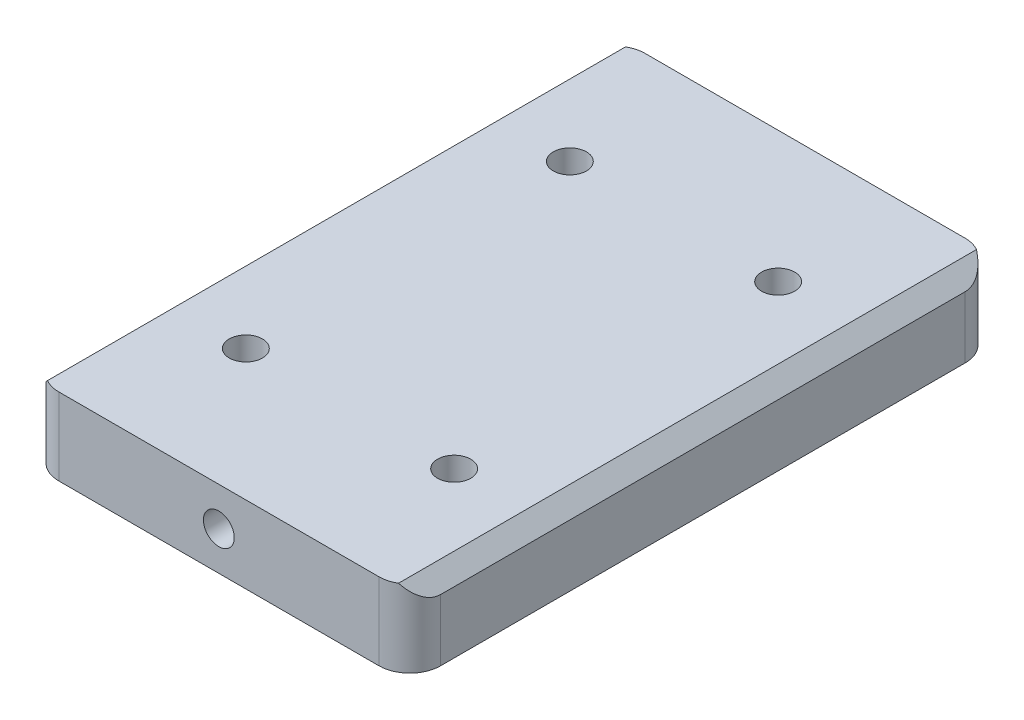
SolidWorks part; units mm, degrees
note: The reader was unsure of these and kept them because the rebuilt part matched: shared geometry of "Sketch1<3>", "Sketch1<5>".
ref_plane "Front Plane" through (0, 0, 0) normal (0, 0, 1) x (1, 0, 0)
ref_plane "Top Plane" through (0, 0, 0) normal (0, 1, 0) x (1, 0, 0)
ref_plane "Right Plane" through (0, 0, 0) normal (1, 0, 0) x (0, 0, -1)
sketch "Base" plane through (0, 0, 0) normal (0, 1, 0) x (1, 0, 0)
  line L0 (0, 0) -> (12.375, 0) construction
  line L1 (-12.375, 19) -> (12.375, 19)
  line L2 (-12.375, 19) -> (-12.375, -19)
  line L3 (-12.375, -19) -> (12.375, -19)
  line L4 (12.375, 19) -> (12.375, -19)
  line L5 (-12.375, 19) -> (12.375, -19) construction
  line L6 (-12.375, -19) -> (12.375, 19) construction
  line L7 (-6.75, 10.5) -> (-6.75, -10.5) construction
  line L8 (-6.75, 10.5) -> (6.75, 10.5) construction
  line L9 (-6.75, -10.5) -> (6.75, -10.5) construction
  line L10 (6.75, 10.5) -> (6.75, -10.5) construction
  line L11 (0, 11.2146) -> (0, -9.7854) construction
  line L12 (-4.75, 9.3453) -> (-4.75, 11.6547)
  line L13 (-4.75, 11.6547) -> (-6.75, 12.8094)
  line L14 (-6.75, 12.8094) -> (-8.75, 11.6547)
  line L15 (-8.75, 11.6547) -> (-8.75, 9.3453)
  line L16 (-8.75, 9.3453) -> (-6.75, 8.1906)
  line L17 (-6.75, 8.1906) -> (-4.75, 9.3453)
  line L18 (8.75, 11.6547) -> (6.75, 12.8094)
  line L19 (6.75, 12.8094) -> (4.75, 11.6547)
  line L20 (4.75, 11.6547) -> (4.75, 9.3453)
  line L21 (4.75, 9.3453) -> (6.75, 8.1906)
  line L22 (6.75, 8.1906) -> (8.75, 9.3453)
  line L23 (8.75, 9.3453) -> (8.75, 11.6547)
  line L24 (8.75, -11.6547) -> (8.75, -9.3453)
  line L25 (8.75, -9.3453) -> (6.75, -8.1906)
  line L26 (6.75, -8.1906) -> (4.75, -9.3453)
  line L27 (4.75, -9.3453) -> (4.75, -11.6547)
  line L28 (4.75, -11.6547) -> (6.75, -12.8094)
  line L29 (6.75, -12.8094) -> (8.75, -11.6547)
  line L30 (-4.75, -11.6547) -> (-4.75, -9.3453)
  line L31 (-4.75, -9.3453) -> (-6.75, -8.1906)
  line L32 (-6.75, -8.1906) -> (-8.75, -9.3453)
  line L33 (-8.75, -9.3453) -> (-8.75, -11.6547)
  line L34 (-8.75, -11.6547) -> (-6.75, -12.8094)
  line L35 (-6.75, -12.8094) -> (-4.75, -11.6547)
  line L36 (-6.75, 0) -> (6.75, 0) construction
  circle A0 centre (-6.75, 10.5) radius 1.075
  circle A1 centre (6.75, 10.5) radius 1.075
  circle A2 centre (6.75, -10.5) radius 1.075
  circle A3 centre (-6.75, -10.5) radius 1.075
  circle A4 centre (-6.75, 10.5) radius 2 construction
  circle A5 centre (6.75, 10.5) radius 2 construction
  circle A6 centre (6.75, -10.5) radius 2 construction
  circle A7 centre (-6.75, -10.5) radius 2 construction
  point P0 (0, 0)
  point P45 (0, 0)
  dimension "D5" = 2.15
  dimension "D6" = 4
  dimension "D1" = 24.75
  dimension "D2" = 38
  dimension "D3" = 13.5
  dimension "D4" = 21
extrude "Boss-Extrude1" add sketch "Base" along normal blind 5 contours L4 L1 L2 L3 L35 L34 L33 L32 L31 L30 L29 L28 L27 L26 L25 L24 L23 L22 L21 L20 L19 L18 L17 L16 L15 L14 L13 L12 | A3 | L28 L29 L24 L25 L26 L27 A2 | A2 | L22 L23 L18 L19 L20 L21 A1 | A0 | L16 L17 L12 L13 L14 L15 A0 | A1 | L34 L35 L30 L31 L32 L33 A3
extrude "Cut-Extrude1" cut sketch "Sketch1<3>" along normal blind 2 contours L16 L17 L12 L13 L14 L15 A0 | A0 | L34 L35 L30 L31 L32 L33 A3 | A3 | L28 L29 L24 L25 L26 L27 A2 | A2 | L22 L23 L18 L19 L20 L21 A1 | A1
sketch "Sketch1<3>" plane through (0, 0, 0) normal (0, 1, 0) x (1, 0, 0) same geometry as "Base"
extrude "Cut-Extrude2" cut sketch "Sketch1<5>" along normal through all contours A1 | A2 | A3 | A0
sketch "Sketch1<5>" plane through (0, 0, 0) normal (0, 1, 0) x (1, 0, 0) same geometry as "Base"
fillet "Fillet1" radius 2 4 edges at (12.375, 2.5, 19) (-12.375, 2.5, 19) (-12.375, 2.5, -19) (12.375, 2.5, -19)
chamfer "Chamfer1" distance 1 angle 45 2 edges at (-12.375, 5, 0) (12.375, 5, 0)
sketch "Mount_Hole" plane through (0, 0, -19) normal (0, 0, -1) x (-1, 0, 0)
  line L0 (0, 0) -> (0, 5) construction
  line L1 (10.375, 0) -> (-10.375, 0) construction
  line L3 (10.375, 5) -> (-10.375, 5) construction
  circle A0 centre (0, 2.5) radius 1
  point P4 (0, 2.5)
  dimension "D1" = 2
extrude "Cut-Extrude3" cut sketch "Mount_Hole" against normal blind 7.5
ref_plane "Plane1" through (0, 0, 0) normal (0, 0, -1) x (-1, 0, 0)
mirror "Mirror1" about plane through (0, 0, 0) normal (0, 0, -1) of "Cut-Extrude3"
